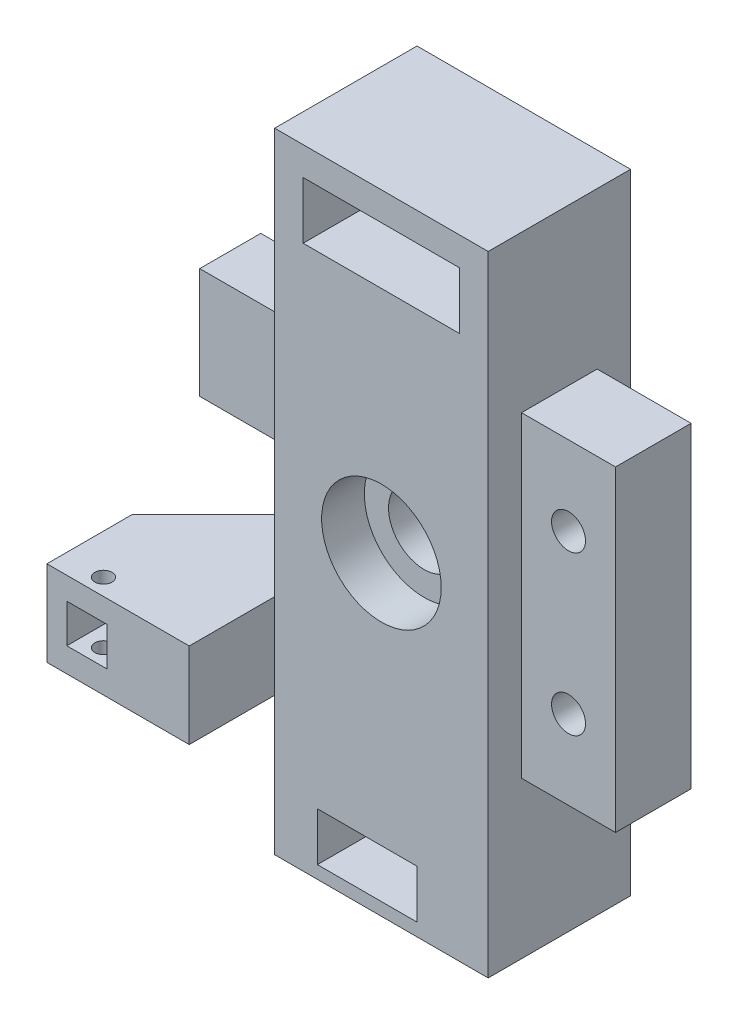
SolidWorks part; units mm, degrees
ref_plane "Front Plane" through (0, 0, 0) normal (0, 0, 1) x (1, 0, 0)
ref_plane "Top Plane" through (0, 0, 0) normal (0, 1, 0) x (1, 0, 0)
ref_plane "Right Plane" through (0, 0, 0) normal (1, 0, 0) x (0, 0, -1)
sketch "Sketch1" plane through (0, 0, 0) normal (0, 1, 0) x (1, 0, 0)
  line L1 (-37.5, -25) -> (37.5, -25)
  line L2 (-37.5, -25) -> (-37.5, 25)
  line L3 (-37.5, 25) -> (37.5, 25)
  line L4 (37.5, -25) -> (37.5, 25)
  line L5 (-37.5, -25) -> (37.5, 25) construction
  line L6 (-37.5, 25) -> (37.5, -25) construction
  point P0 (0, 0)
  dimension "D1" = 50
  dimension "D2" = 75
extrude "BE - main upright body" add sketch "Sketch1" along normal blind 221 contours L3 L4 L1 L2
sketch "Sketch2" plane through (0, 0, 25) normal (0, 0, 1) x (1, 0, 0)
  line L0 (-37.5, 221) -> (37.5, 0) construction
  line L1 (-37.5, 0) -> (37.5, 221) construction
  circle A0 centre (0, 110.5) radius 21
  point P10 (0, 110.5)
  dimension "D1" = 42
sketch "Sketch3" plane through (0, 0, -25) normal (0, 0, -1) x (-1, 0, 0)
  line L0 (-37.5, 0) -> (37.5, 221) construction
  line L1 (-37.5, 221) -> (37.5, 0) construction
  circle A0 centre (0, 110.5) radius 23.5
  point P10 (0, 110.5)
  dimension "D1" = 47
sketch "Sketch4" plane through (0, 0, 25) normal (0, 0, 1) x (1, 0, 0)
  line L0 (-37.5, 221) -> (37.5, 0) construction
  line L1 (37.5, 221) -> (-37.5, 0) construction
  line L2 (-37.5, 0) -> (37.5, 0) construction
  circle A0 centre (0, 110.5) radius 12.5
  dimension "D1" = 25
extrude "CE - Through hole" cut sketch "Sketch4" against normal through all
extrude "CE - Inner bearing" cut sketch "Sketch2" against normal blind 15 contours A0
extrude "CE - Outer bearing" cut sketch "Sketch3" against normal blind 15 contours A0
sketch "Sketch7" plane through (37.5, 0, 0) normal (1, 0, 0) x (0, 0, -1)
  line L0 (25, 221) -> (25, 0) construction
  line L1 (-13.2754, 54.9027) -> (13.2754, 54.9027)
  line L2 (-13.2754, 54.9027) -> (-13.2754, 166.0973)
  line L3 (-13.2754, 166.0973) -> (13.2754, 166.0973)
  line L4 (13.2754, 54.9027) -> (13.2754, 166.0973)
  line L5 (-13.2754, 54.9027) -> (13.2754, 166.0973) construction
  line L6 (-13.2754, 166.0973) -> (13.2754, 54.9027) construction
  line L7 (-25, 110.5) -> (25, 110.5) construction
  line L8 (-25, 221) -> (-25, 0) construction
  point P0 (0, 110.5)
  point P12 (0, 110.5)
extrude "BE - caliper mount" add sketch "Sketch7" along normal blind 33
sketch "Sketch8" plane through (-37.5, 0, 0) normal (-1, 0, 0) x (0, 0, 1)
  line L1 (-3.1234, 119.5732) -> (18.3177, 119.5732)
  line L2 (-3.1234, 119.5732) -> (-3.1234, 158.4522)
  line L3 (-3.1234, 158.4522) -> (18.3177, 158.4522)
  line L4 (18.3177, 119.5732) -> (18.3177, 158.4522)
  line L5 (-3.1234, 119.5732) -> (18.3177, 158.4522) construction
  line L6 (-3.1234, 158.4522) -> (18.3177, 119.5732) construction
  point P0 (7.5971, 139.0127)
extrude "BE - temp sensor mount" add sketch "Sketch8" along normal blind 33
sketch "Sketch9" plane through (-37.5, 0, 0) normal (-1, 0, 0) x (0, 0, 1)
  line L0 (25, 89.5) -> (25, 131.5) construction
  line L1 (-5, 48.5) -> (55, 48.5)
  line L2 (-5, 48.5) -> (-5, 78.5)
  line L3 (-5, 78.5) -> (55, 78.5)
  line L4 (55, 48.5) -> (55, 78.5)
  line L5 (-5, 48.5) -> (55, 78.5) construction
  line L6 (-5, 78.5) -> (55, 48.5) construction
  line L7 (25, 89.5) -> (25, 131.5) construction
  line L8 (25, 221) -> (25, 0) construction
  point P0 (25, 63.5)
  point P7 (25, 110.5)
  dimension "D1" = 47
  dimension "D2" = 60
  dimension "D3" = 30
extrude "BE - tie rod mount" add sketch "Sketch9" along normal blind 50
sketch "Sketch10" plane through (0, 0, 13.2754) normal (0, 0, 1) x (1, 0, 0)
  line L0 (54, 166.0973) -> (54, 54.9027) construction
  line L1 (70.5, 166.0973) -> (37.5, 166.0973) construction
  line L2 (70.5, 54.9027) -> (37.5, 54.9027) construction
  line L3 (37.5, 166.0973) -> (70.5, 110.5) construction
  line L4 (70.5, 166.0973) -> (70.5, 54.9027) construction
  line L5 (70.5, 166.0973) -> (37.5, 110.5) construction
  line L6 (37.5, 166.0973) -> (37.5, 54.9027) construction
  line L7 (37.5, 110.5) -> (70.5, 54.9027) construction
  line L8 (37.5, 54.9027) -> (70.5, 110.5) construction
  circle A0 centre (54, 138.2986) radius 5.968
  circle A1 centre (54, 82.7014) radius 5.968
  point P20 (54, 138.2986)
extrude "CE - caliper holes" cut sketch "Sketch10" against normal through all
sketch "Sketch12" plane through (0, 0, 25) normal (0, 0, 1) x (1, 0, 0)
  line L0 (-12.5, 201) -> (12.5, 201) construction
  line L2 (-37.5, 221) -> (37.5, 221) construction
  circle A0 centre (-12.5, 201) radius 4
  circle A1 centre (12.5, 201) radius 4
  point P2 (0, 201)
  dimension "D1" = 8
  dimension "D2" = 20
  dimension "D3" = 25
extrude "CE - top clevis holes" cut sketch "Sketch12" against normal through all
sketch "Sketch13" plane through (0, 0, 25) normal (0, 0, 1) x (1, 0, 0)
  line L0 (-37.5, 221) -> (37.5, 221) construction
  line L1 (-27.5, 191) -> (27.5, 191)
  line L2 (-27.5, 191) -> (-27.5, 211)
  line L3 (-27.5, 211) -> (27.5, 211)
  line L4 (27.5, 191) -> (27.5, 211)
  line L5 (-27.5, 191) -> (27.5, 211) construction
  line L6 (-27.5, 211) -> (27.5, 191) construction
  point P0 (0, 201)
  dimension "D1" = 20
  dimension "D2" = 55
  dimension "D3" = 20
extrude "CE - top clevis space" cut sketch "Sketch13" against normal blind 35 contours L3 L4 L1 L2
ref_plane "Top clevis plane" through (0, 0, 5) normal (0, 0, 1) x (1, 0, 0)
ref_point "Position of Top Clevis"
sketch "Sketch14" plane through (0, 0, 25) normal (0, 0, 1) x (1, 0, 0)
  line L1 (-22.48, 4.5) -> (2.52, 4.5)
  line L2 (-22.48, 4.5) -> (-22.48, 16.5)
  line L3 (-22.48, 16.5) -> (2.52, 16.5)
  line L4 (2.52, 4.5) -> (2.52, 16.5)
  line L5 (-22.48, 4.5) -> (2.52, 16.5) construction
  line L6 (-22.48, 16.5) -> (2.52, 4.5) construction
  point P0 (-9.98, 10.5)
  dimension "D1" = 9.98
  dimension "D2" = 190.5
  dimension "D3" = 12
  dimension "D4" = 25
extrude "CE - bottom clevis space" cut sketch "Sketch14" against normal through all
ref_plane "Bottom Clevis Plane" through (0, 0, -1.65) normal (0, 0, 1) x (1, 0, 0)
ref_point "Position of Bottom Clevis"
sketch "Sketch15" plane through (0, 0, 25) normal (0, 0, 1) x (1, 0, 0)
  line L0 (2.52, 4.5) -> (2.52, 16.5) construction
  line L1 (-22.48, 16.5) -> (2.52, 16.5)
  line L2 (-22.48, 16.5) -> (-22.48, 21.5)
  line L3 (-22.48, 21.5) -> (2.52, 21.5)
  line L4 (2.52, 16.5) -> (2.52, 21.5)
  dimension "D1" = 5
extrude "CE - expand bottom clevis" cut sketch "Sketch15" against normal through all
ref_plane "P - front of part" through (2.52, 4.5, 25) normal (0, 0, 1) x (1, 0, 0)
sketch "Sketch16" plane through (2.52, 4.5, 25) normal (0, 0, 1) x (1, 0, 0)
  line L0 (0, 17) -> (-25, 17) construction
  line L1 (0, 0) -> (10.0076, 0)
  line L2 (0, 0) -> (0, 17)
  line L3 (0, 17) -> (10.0076, 17)
  line L4 (10.0076, 0) -> (10.0076, 17)
  dimension "D1" = 10.0076
extrude "CE - widen bottom clevis" cut sketch "Sketch16" against normal through all and the other way through all
chamfer "Chamfer1" distance 30 angle 45 1 edges at (-87.5, 63.5, -5)
ref_plane "P - xy plane containing bottom clevis" through (0, 10.5, 0) normal (0, 1, 0) x (1, 0, 0)
ref_plane "P - xy plane containing tie rod" through (0, 63.84, 0) normal (0, 1, 0) x (1, 0, 0)
sketch "Sketch17" plane through (0, 63.84, 0) normal (0, 1, 0) x (1, 0, 0)
  point P0 (-73.48, -49.15)
  point P1 (-9.98, 1.65)
  point P3 (-9.98, 1.65)
  dimension "D1" = 63.5
  dimension "D2" = 50.8
ref_point "Position of Tie Rod"
sketch "Sketch18" plane through (0, 0, 55) normal (0, 0, 1) x (1, 0, 0)
  line L1 (-80.502, 57.0586) -> (-66.458, 57.0586)
  line L2 (-80.502, 57.0586) -> (-80.502, 70.6214)
  line L3 (-80.502, 70.6214) -> (-66.458, 70.6214)
  line L4 (-66.458, 57.0586) -> (-66.458, 70.6214)
  line L5 (-80.502, 57.0586) -> (-66.458, 70.6214) construction
  line L6 (-80.502, 70.6214) -> (-66.458, 57.0586) construction
  point P0 (-73.48, 63.84)
  point P2 (-73.48, 63.84)
extrude "Cut-Extrude1" cut sketch "Sketch18" against normal blind 20
sketch "Sketch19" plane through (0, 78.5, 0) normal (0, 1, 0) x (1, 0, 0)
  circle A0 centre (-73.48, -49.15) radius 3
  point P2 (-73.48, -49.15)
  dimension "D1" = 6
extrude "Cut-Extrude2" cut sketch "Sketch19" against normal through all
equation "\"clevis_pin_y\"=20"
equation "\"D2@Sketch12\"=\"clevis_pin_y\""
equation "\"clevis_pin_dist\"=25"
equation "\"D3@Sketch12\"=\"clevis_pin_dist\""
equation "\"D2@Sketch13\"=\"clevis_pin_dist\" + 30"
equation "\"D1@Sketch13\"=\"clevis_pin_y\""
equation "\"x_dist_a_arms\"=9.98"
equation "\"D1@Sketch14\"=\"x_dist_a_arms\""
equation "\"y_dist_a_arms\"=190.5"
equation "\"D2@Sketch14\"=\"y_dist_a_arms\""
equation "\"y_dist_bottom_clevis_to_tie_rod\"= 53.34"
equation "\"x_dist_bottom_clevis_to_tie_rod\"= 63.50"
equation "\"z_dist_bottom_clevis_to_tie_rod\"= 50.80"
